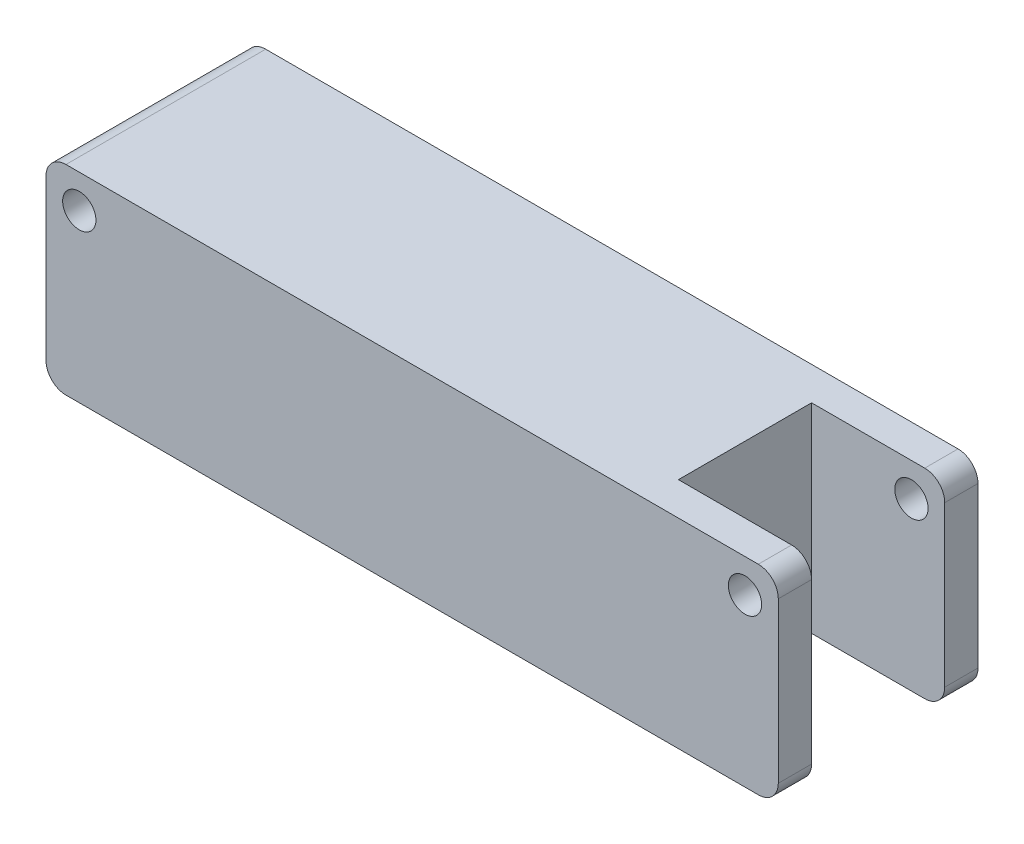
SolidWorks part; units mm, degrees
ref_plane "Plan de face" through (0, 0, 0) normal (0, 0, 1) x (1, 0, 0)
ref_plane "Plan de dessus" through (0, 0, 0) normal (0, 1, 0) x (1, 0, 0)
ref_plane "Plan de droite" through (0, 0, 0) normal (1, 0, 0) x (0, 0, -1)
other "Centre de masse"
sketch "Esquisse2" plane through (0, 0, 0) normal (0, 1, 0) x (1, 0, 0)
  line L0 (0, 0) -> (56.0293, 0) construction
  line L1 (0, -15) -> (110, -15)
  line L2 (0, -15) -> (0, 15)
  line L3 (0, 15) -> (110, 15)
  line L4 (110, -15) -> (110, 15)
  line L5 (0, 0) -> (0, -42.7765) construction
  dimension "D1" = 110
  dimension "D2" = 30
extrude "Boss.-Extru.1" add sketch "Esquisse2" along normal mid plane 30
fillet "Congé1" radius 3 4 edges at (0, 15, 0) (110, 15, 0) (110, -15, 0) (0, -15, 0)
sketch "Esquisse4" plane through (0, 15, 0) normal (0, 1, 0) x (1, 0, 0)
  line L0 (110, 15) -> (110, -15) construction
  line L1 (110, 10) -> (110, -10)
  line L2 (110, -10) -> (90, -10)
  line L4 (90, -10) -> (90, 10)
  line L6 (90, 10) -> (110, 10)
  line L7 (3, -15) -> (107, -15) construction
  line L8 (63.6485, 0) -> (81.8664, 0) construction
  dimension "D1" = 20
  dimension "D2" = 5
extrude "Enlèv. mat.-Extru.1" cut sketch "Esquisse4" against normal through all
sketch "Esquisse5" plane through (0, 0, -15) normal (0, 0, -1) x (-1, 0, 0)
  line L0 (-107, 15) -> (-3, 15) construction
  line L1 (-110, 12) -> (-110, -12) construction
  line L2 (-55, 0) -> (-55, 9.0949) construction
  circle A0 centre (-105, 10) radius 2.5
  circle A1 centre (-5, 10) radius 2.5
  dimension "D1" = 5
  dimension "D2" = 5
  dimension "D3" = 5
  dimension "D4" = 55
extrude "Enlèv. mat.-Extru.2" cut sketch "Esquisse5" against normal through all
ref_axis "Axe1" through (5, 10, 15) along (0, 0, -1)
ref_point "Point1"
ref_axis "Axe2" through (105, 10, 15) along (0, 0, -1)
ref_point "Point2"
equation "\"L\"= 0.03m"
equation "\"ldoigt\"= 0.11m"
equation "\"D1@Esquisse2\"=\"ldoigt\""
equation "\"D2@Esquisse2\"=\"L\""
equation "\"e\"= 0.03m"
equation "\"D1@Congé1\"=\"e\"/10m"
equation "\"D4@Esquisse5\"=\"ldoigt\"/2"
